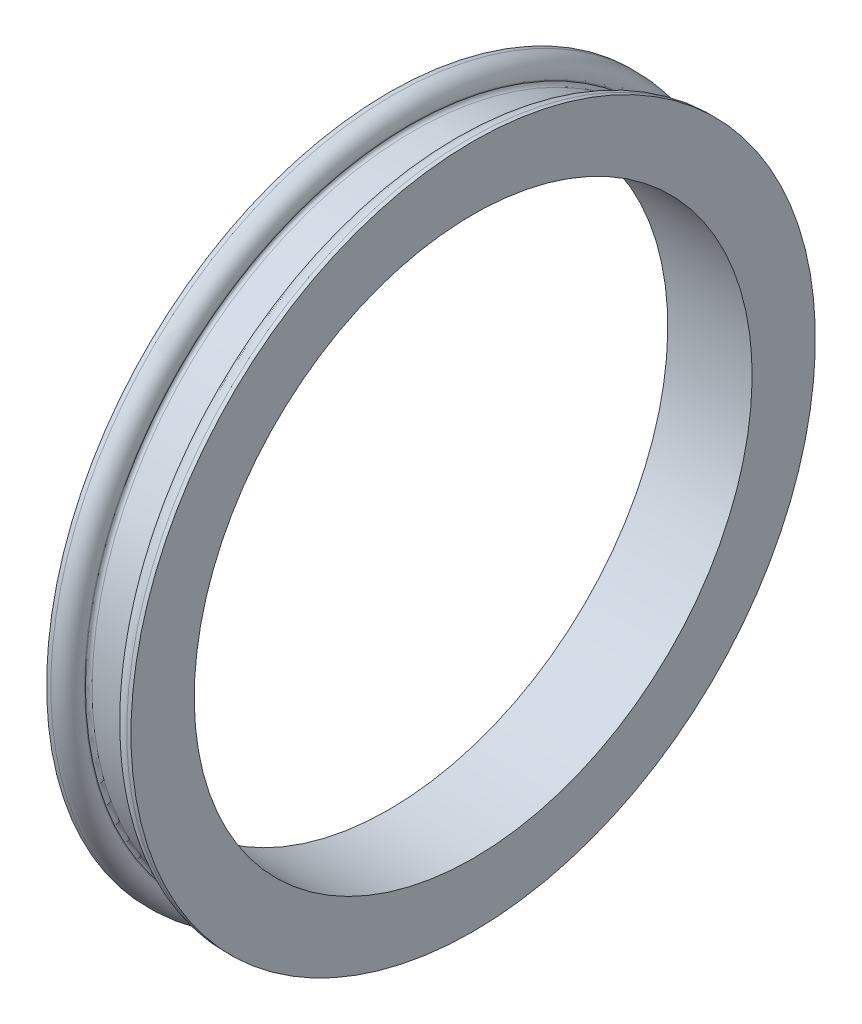
SolidWorks part; units mm, degrees
material "Nylon 101"
ref_plane "Front Plane" through (0, 0, 0) normal (0, 0, 1) x (1, 0, 0)
ref_plane "Top Plane" through (0, 0, 0) normal (0, 1, 0) x (1, 0, 0)
ref_plane "Right Plane" through (0, 0, 0) normal (1, 0, 0) x (0, 0, -1)
sketch "Sketch1" plane through (0, 0, 0) normal (0, 0, 1) x (1, 0, 0)
  line L0 (-11.2276, 0) -> (11.2276, 0) construction
  line L1 (0, 0) -> (0, 21) construction
  line L2 (-3.175, 21) -> (3.175, 21)
  line L3 (-3.175, 21) -> (-3.175, 25.7625)
  line L4 (0, 21) -> (0, 24.175) construction
  line L5 (-1.3335, 24.175) -> (1.3335, 24.175)
  line L6 (3.175, 21) -> (3.175, 25.7625)
  line L7 (-1.5875, 24.429) -> (-1.5875, 24.4925)
  line L8 (-2.8575, 25.7625) -> (-3.175, 25.7625)
  line L9 (1.5875, 24.429) -> (1.5875, 24.4925)
  line L10 (2.8575, 25.7625) -> (3.175, 25.7625)
  arc A0 (-1.5875, 24.4925) -> (-2.8575, 25.7625) centre (-2.8575, 24.4925) ccw
  arc A1 (2.8575, 25.7625) -> (1.5875, 24.4925) centre (2.8575, 24.4925) ccw
  arc A2 (-1.5875, 24.429) -> (-1.3335, 24.175) centre (-1.3335, 24.429) ccw
  arc A3 (1.3335, 24.175) -> (1.5875, 24.429) centre (1.3335, 24.429) ccw
  point P20 (-1.5875, 24.175)
  point P23 (1.5875, 24.175)
  dimension "D6" = 1.27
  dimension "D7" = 1.27
  dimension "D8" = 0.254
  dimension "D9" = 0.254
  dimension "D1" = 21
  dimension "D2" = 1.5875
  dimension "D3" = 4.7625
  dimension "D4" = 3.175
  dimension "D5" = 1.5875
  dimension "D10" = 1.5875
  dimension "D11" = 1.5875
revolve "Revolve1" add sketch "Sketch1" angle 360 about L0
